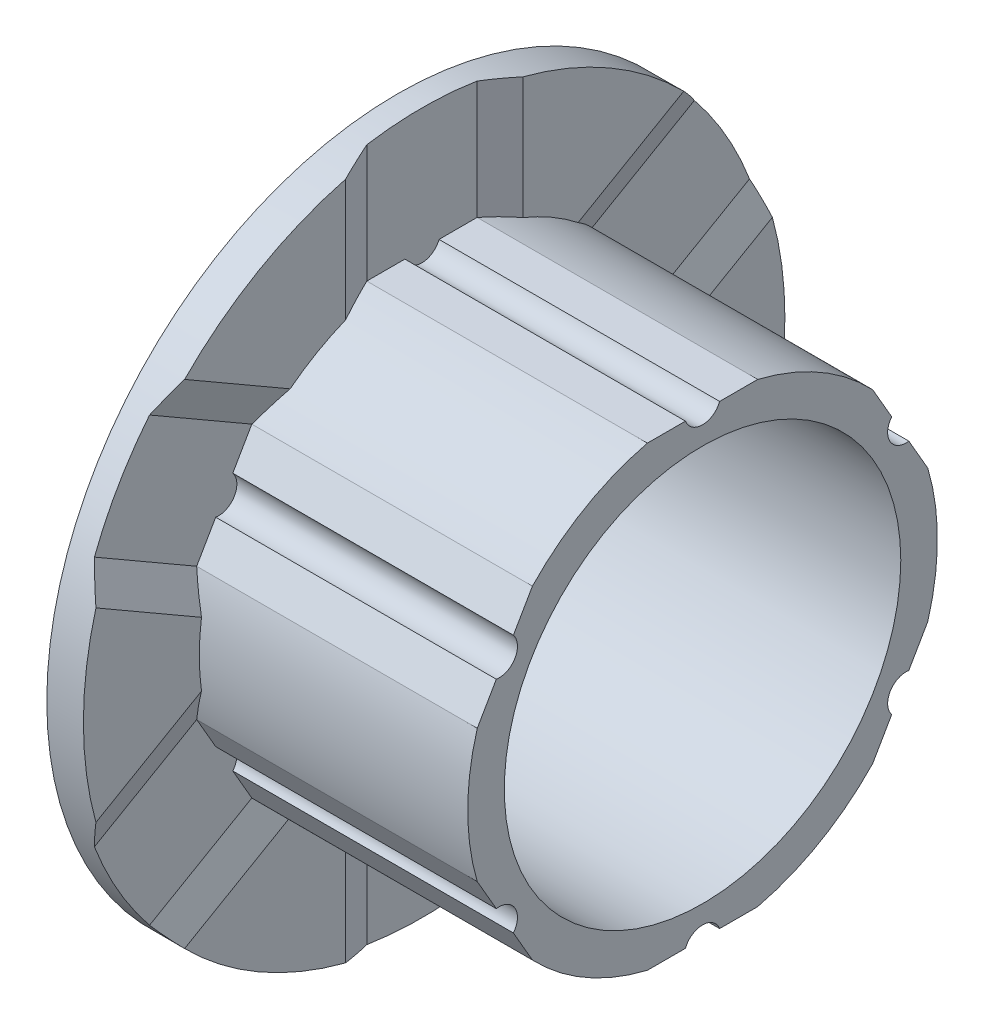
SolidWorks part; units mm, degrees
ref_plane "Front Plane" through (0, 0, 0) normal (0, 0, 1) x (1, 0, 0)
ref_plane "Top Plane" through (0, 0, 0) normal (0, 1, 0) x (1, 0, 0)
ref_plane "Right Plane" through (0, 0, 0) normal (1, 0, 0) x (0, 0, -1)
sketch "Sketch1" plane through (0, 0, 0) normal (1, 0, 0) x (0, 0, -1)
  circle A0 centre (0, 0) radius 6.5
  circle A1 centre (0, 0) radius 7.7
  dimension "D1" = 13
  dimension "D2" = 1.2
extrude "Boss-Extrude1" add sketch "Sketch1" along normal blind 10
sketch "Sketch2" plane through (0, 0, 0) normal (-1, 0, 0) x (0, 0, 1)
  circle A0 centre (0, 0) radius 11.5
  circle A1 centre (0, 0) radius 7.7
  circle A2 centre (0, 0) radius 7.7
  dimension "D2" = 23
  dimension "D1" = 0
extrude "Boss-Extrude2" add sketch "Sketch2" against normal blind 1.2
sketch "Sketch5" plane through (10, 0, 0) normal (1, 0, 0) x (0, 0, -1)
  line L0 (0, 7.7) -> (0, 0) construction
  circle A0 centre (0, 7.7) radius 0.6
  circle A1 centre (0, 0) radius 7.7 construction
  circle A2 centre (0, 0) radius 7.7 construction
  dimension "D1" = 1.2
extrude "Cut-Extrude4" cut sketch "Sketch5" against normal up to surface (8.8 mm away) up to face at (1.2, 0, 7.7)
chamfer "Chamfer4" distance 0.5 angle 70 2 edges at (5.6, 7.6766, -0.5995) (5.6, 7.6766, 0.5995) first distance on face at (5.6, 7.3883, 0)
sketch "Sketch6" plane through (1.2, 0, 0) normal (1, 0, 0) x (0, 0, -1)
  line L0 (0.56, 7.4846) -> (1.8078, 7.4848) construction
  line L1 (-1.8078, 7.4848) -> (-0.56, 7.4846) construction
  line L2 (0.56, 7.4846) -> (1.8078, 7.4848)
  line L3 (-1.8078, 7.4848) -> (-0.56, 7.4846)
  line L4 (-1.8078, 7.4848) -> (-1.8078, 11.357)
  line L5 (1.8078, 7.4848) -> (1.8078, 11.357)
  arc A0 (-0.56, 7.4846) -> (0.56, 7.4846) centre (0, 7.7) ccw construction
  arc A1 (-0.56, 7.4846) -> (0.56, 7.4846) centre (0, 7.7) ccw
  circle A2 centre (0, 0) radius 11.5 construction
  arc A3 (-1.8078, 11.357) -> (1.8078, 11.357) centre (0, 0) cw
extrude "Cut-Extrude5" cut sketch "Sketch6" against normal blind 0.4
chamfer "Chamfer5" distance 0.4 angle 70 2 edges at (1.2, 9.4209, 1.8078) (1.2, 9.4209, -1.8078) first distance on face at (1, 9.4209, 1.8078) first distance on face at (1, 9.4209, -1.8078)
pattern_circular "CirPattern2" count 6 over 360 about axis through (10, 0, 0) along (-1, 0, 0) of "Chamfer5", "Cut-Extrude4", "Cut-Extrude5", "Chamfer4" reverse direction yes
